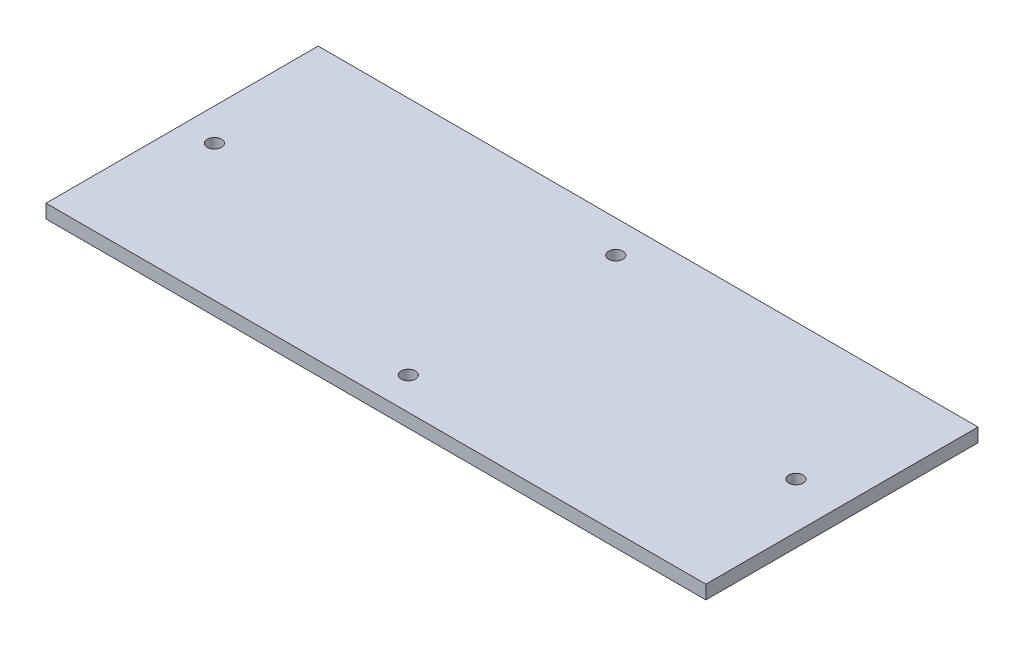
SolidWorks part; units mm, degrees
ref_plane "Front Plane" through (0, 0, 0) normal (0, 0, 1) x (1, 0, 0)
ref_plane "Top Plane" through (0, 0, 0) normal (0, 1, 0) x (1, 0, 0)
ref_plane "Right Plane" through (0, 0, 0) normal (1, 0, 0) x (0, 0, -1)
sketch "Sketch1" plane through (0, 0, 0) normal (0, 1, 0) x (1, 0, 0)
  line L0 (0, 31.5875) -> (0, -31.5875) construction
  line L1 (-76.5875, 31.5875) -> (76.5875, 31.5875)
  line L2 (-76.5875, 31.5875) -> (-76.5875, -31.5875)
  line L3 (-76.5875, -31.5875) -> (76.5875, -31.5875)
  line L4 (76.5875, 31.5875) -> (76.5875, -31.5875)
  line L5 (-76.5875, 31.5875) -> (76.5875, -31.5875) construction
  line L6 (-76.5875, -31.5875) -> (76.5875, 31.5875) construction
  line L7 (-69.0875, 24.0875) -> (65.9125, 24.0875) construction
  line L8 (-69.0875, 24.0875) -> (-69.0875, -24.0875) construction
  line L9 (-69.0875, -24.0875) -> (65.9125, -24.0875) construction
  line L10 (65.9125, 24.0875) -> (65.9125, -24.0875) construction
  line L11 (-76.5875, 0) -> (76.5875, 0) construction
  circle A0 centre (0, 24.0875) radius 1.65
  circle A1 centre (-69.0875, 0) radius 1.65
  circle A2 centre (65.9125, 0) radius 1.65
  circle A3 centre (0, -24.0875) radius 1.65
  point P0 (0, 0)
  point P6 (0, 0)
  point P23 (0, 0)
  point P24 (0, 0)
  dimension "D7" = 3.3
  dimension "D1" = 153.175
  dimension "D2" = 7.5
  dimension "D3" = 7.5
  dimension "D4" = 10.675
  dimension "D5" = 7.5
  dimension "D6" = 63.175
extrude "Boss-Extrude1" add sketch "Sketch1" along normal blind 3.175
